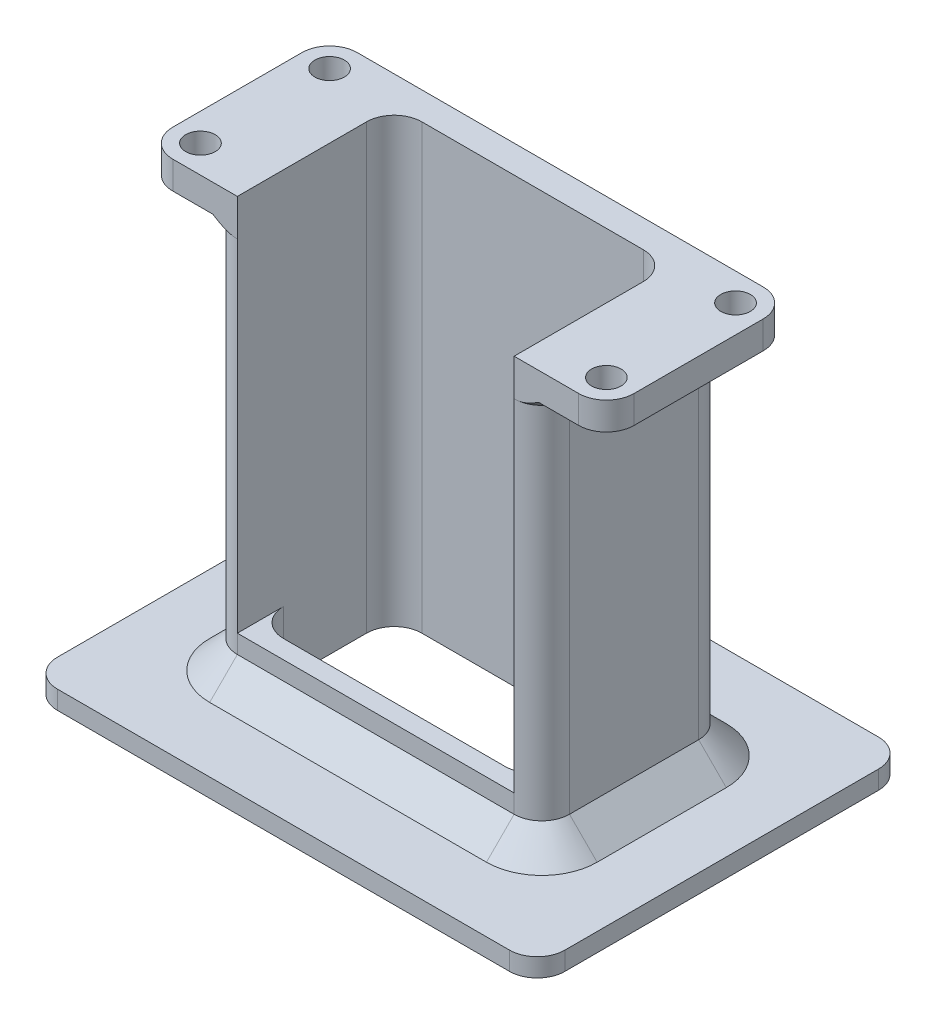
SolidWorks part; units mm, degrees
ref_plane "前视基准面" through (0, 0, 0) normal (0, 0, 1) x (1, 0, 0)
ref_plane "上视基准面" through (0, 0, 0) normal (0, 1, 0) x (1, 0, 0)
ref_plane "右视基准面" through (0, 0, 0) normal (1, 0, 0) x (0, 0, -1)
sketch "草图1" plane through (0, 0, 0) normal (0, 1, 0) x (1, 0, 0)
  line L0 (15, 10) -> (15, -10)
  line L1 (-25, -10) -> (25, -10)
  line L2 (-25, -10) -> (-25, 10)
  line L3 (-25, 10) -> (25, 10)
  line L4 (25, -10) -> (25, 10)
  line L5 (-25, -10) -> (25, 10) construction
  line L6 (-25, 10) -> (25, -10) construction
  line L7 (0, 0) -> (0, -18.0978) construction
  line L8 (-15, 10) -> (-15, -10)
  line L9 (18, 10) -> (18, -10)
  line L10 (-18, 10) -> (-18, -10)
  line L11 (-15, 7) -> (15, 7)
  point P0 (0, 0)
  dimension "D1" = 20
  dimension "D2" = 50
  dimension "D3" = 10
  dimension "D4" = 36
  dimension "D5" = 3
  dimension "D6" = 3
extrude "凸台-拉伸1" add sketch "草图1" against normal blind 45 contours L9 L3 L0 L1 | L8 L11 L0 L3 | L3 L10 L1 L8 region at (16.5, 0, 0) region at (0, 0, -8.5) region at (-16.5, 0, 0)
extrude "凸台-拉伸2" add sketch "草图1<3>" along normal blind 3 contours L10 L3 L2 L1 | L3 L10 L1 L8 | L8 L11 L0 L3 | L9 L3 L0 L1 | L3 L9 L1 L4 region at (16.5, 0, 0) region at (0, 0, -8.5) region at (-16.5, 0, 0) region at (21.5, 0, 0) region at (-21.5, 0, 0)
sketch "草图1<3>" plane through (0, 0, 0) normal (0, 1, 0) x (1, 0, 0) same geometry as "草图1"
sketch "草图2" plane through (0, -45, 0) normal (0, -1, 0) x (1, 0, 0)
  line L0 (18, 0) -> (-18, 0) construction
  line L1 (18, -10) -> (18, 10) construction
  line L3 (-18, -10) -> (-18, 10) construction
  line L5 (-27.5, -20) -> (27.5, -20)
  line L6 (-27.5, -20) -> (-27.5, 20)
  line L7 (-27.5, 20) -> (27.5, 20)
  line L8 (27.5, -20) -> (27.5, 20)
  line L9 (-27.5, -20) -> (27.5, 20) construction
  line L10 (-27.5, 20) -> (27.5, -20) construction
  point P5 (0, 0)
  dimension "D1" = 40
  dimension "D2" = 55
extrude "凸台-拉伸3" add sketch "草图2" against normal blind 2
sketch "草图3" plane through (0, -43, 0) normal (0, 1, 0) x (1, 0, 0)
  line L0 (15, -10) -> (15, 7) construction
  line L1 (-15, -10) -> (15, -10)
  line L2 (-15, -10) -> (-15, -8)
  line L3 (-15, -8) -> (15, -8)
  line L4 (15, -10) -> (15, -8)
  dimension "D1" = 2
extrude "凸台-拉伸4" add sketch "草图3" along normal blind 5
sketch "草图4" plane through (0, -43, 0) normal (0, 1, 0) x (1, 0, 0)
  line L4 (-15, 7) -> (-15, -8)
  line L5 (-15, -8) -> (15, -8)
  line L6 (15, -8) -> (15, 7)
  line L7 (15, 7) -> (-15, 7)
  line L8 (-15, 7) -> (-15, -8)
  line L9 (-15, -8) -> (15, -8)
  line L10 (15, -8) -> (15, 7)
  line L11 (15, 7) -> (-15, 7)
  dimension "D1" = 0
extrude "切除-拉伸1" cut sketch "草图4" against normal through all
sketch "草图6" plane through (0, 3, 0) normal (0, 1, 0) x (1, 0, 0)
  line L0 (-25, 0) -> (-9.4021, 0) construction
  line L1 (-25, -10) -> (-25, 10) construction
  line L3 (0, 0) -> (0, 25) construction
  circle A1 centre (-22, -7) radius 1.6
  circle A2 centre (-22, 7) radius 1.6
  circle A3 centre (22, -7) radius 1.6
  circle A4 centre (22, 7) radius 1.6
  dimension "D1" = 3.2
  dimension "D2" = 14
  dimension "D3" = 3
extrude "切除-拉伸2" cut sketch "草图6" against normal up to next
fillet "圆角1" radius 3 4 edges at (25, 1.5, 10) (25, 1.5, -10) (-25, 1.5, -10) (-25, 1.5, 10)
fillet "圆角2" radius 3 8 edges at (-27.5, -44, 20) (-27.5, -44, -20) (27.5, -44, -20) (27.5, -44, 20) (18, -21.5, 10) (-18, -21.5, 10) (18, -21.5, -10) (-18, -21.5, -10)
chamfer "倒角1" distance 3 angle 45 8 edges at (-18, -43, 0) (-17.1213, -43, 9.1213) (-17.1213, -43, -9.1213) (0, -43, 10) (0, -43, -10) (17.1213, -43, 9.1213) (17.1213, -43, -9.1213) (18, -43, 0)
chamfer "倒角2" distance 1 angle 45 6 edges at (-17.1213, 0, -9.1213) (-17.1213, 0, 9.1213) (-18, 0, 0) (17.1213, 0, -9.1213) (17.1213, 0, 9.1213) (18, 0, 0)
fillet "圆角4" radius 3 4 edges at (15, -41.5, 8) (-15, -41.5, 8) (-15, -21, -7) (15, -21, -7)
